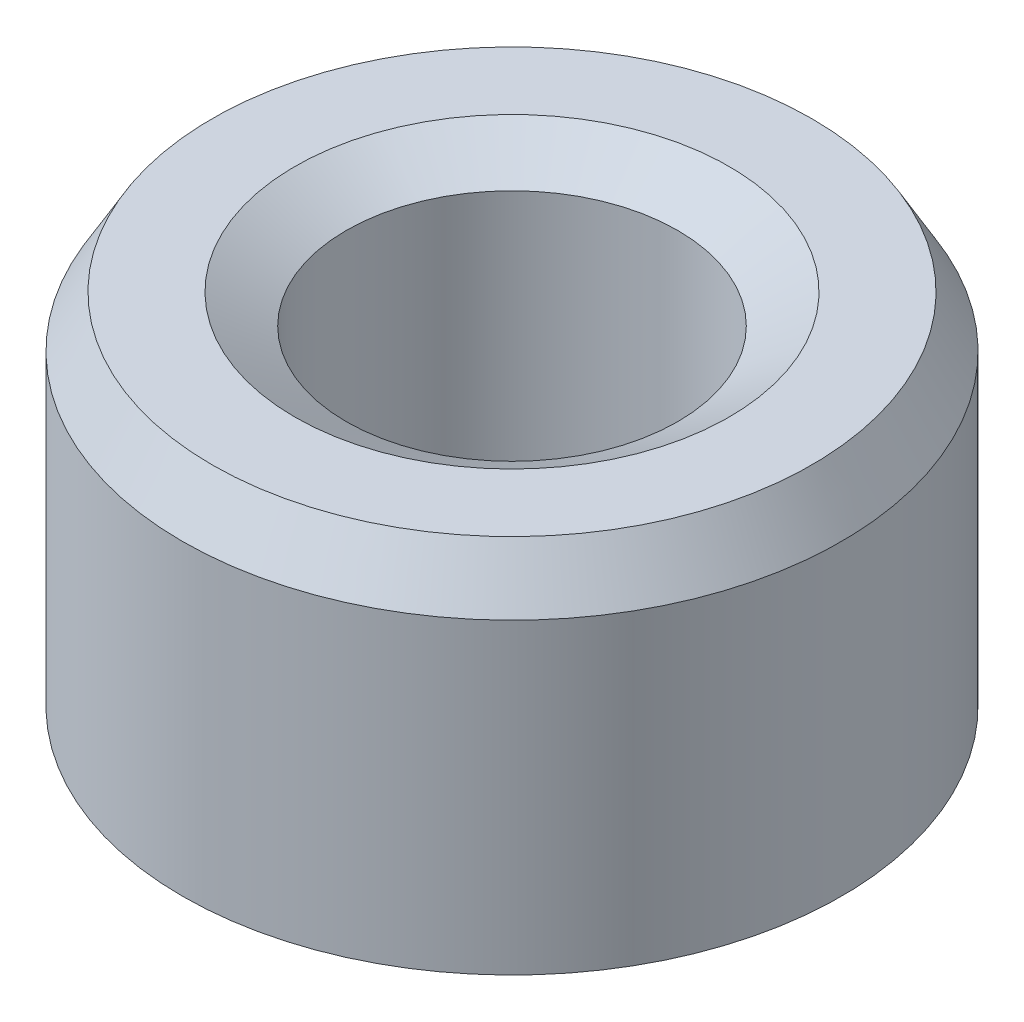
SolidWorks part; units mm, degrees
ref_plane "Front Plane" through (0, 0, 0) normal (0, 0, 1) x (1, 0, 0)
ref_plane "Top Plane" through (0, 0, 0) normal (0, 1, 0) x (1, 0, 0)
ref_plane "Right Plane" through (0, 0, 0) normal (1, 0, 0) x (0, 0, -1)
sketch "Sketch1" plane through (0, 0, 0) normal (0, 1, 0) x (1, 0, 0)
  circle A0 centre (0, 0) radius 7.5
  dimension "SLEEVE_OD" = 15
extrude "Boss-Extrude1" add sketch "Sketch1" along normal blind 8.8394
sketch "Sketch2" plane through (0, 0, 0) normal (0, 1, 0) x (1, 0, 0)
  circle A0 centre (0, 0) radius 3.771
  dimension "BORE_D" = 7.542
extrude "Cut-Extrude1" cut sketch "Sketch2" along normal through all
chamfer "Chamfer1" distance 1.1702 angle 30 4 edges at (0, 8.8394, 3.771) (0, 0, 3.771) (0, 0, 7.5) (0, 8.8394, 7.5) first distance on face at (0, 8.8394, 3.771) first distance on face at (0, 0, 3.771) first distance on face at (0, 8.8394, 7.5)
